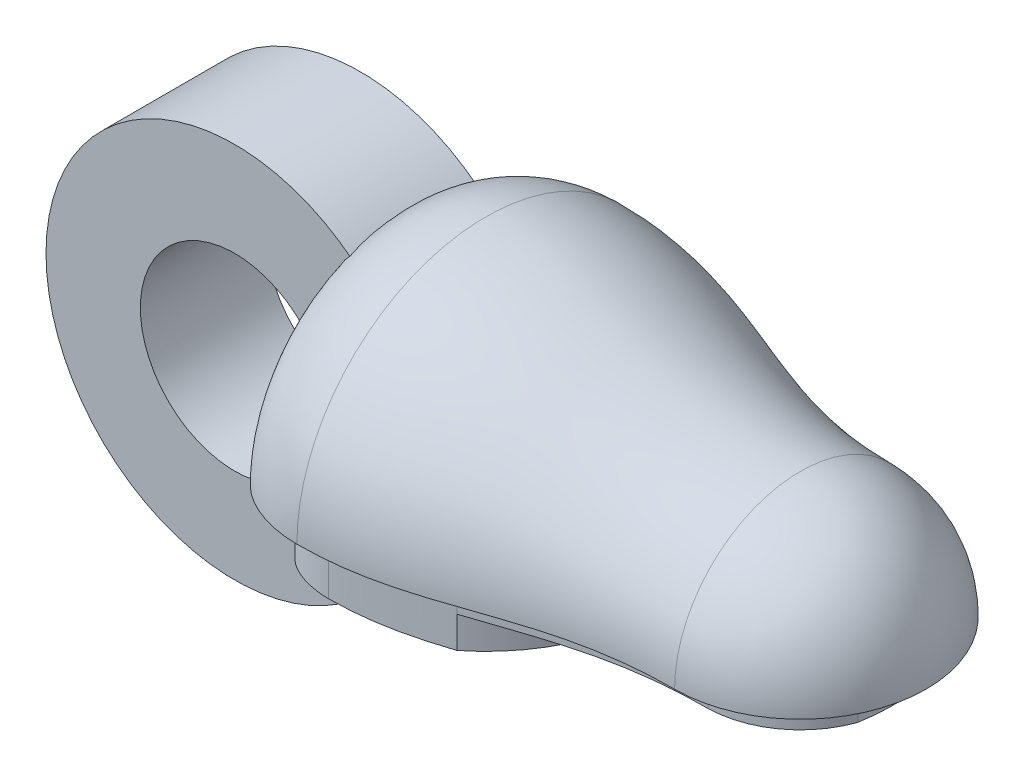
SolidWorks part; units mm, degrees
ref_plane "Front Plane" through (0, 0, 0) normal (0, 0, 1) x (1, 0, 0)
ref_plane "Top Plane" through (0, 0, 0) normal (0, 1, 0) x (1, 0, 0)
ref_plane "Right Plane" through (0, 0, 0) normal (1, 0, 0) x (0, 0, -1)
sketch "Sketch1" plane through (0, 0, 0) normal (0, 1, 0) x (1, 0, 0)
  line L0 (2.6547, 3.7704) -> (-14.3453, 3.7704) construction
  line L1 (-6.9059, 9.7814) -> (-15.9612, 9.7814) construction
  line L2 (1.6216, 7.7704) -> (-4.4887, 7.7704) construction
  line L3 (-11.3453, 5.7814) -> (-11.3453, 3.7704)
  line L4 (-11.3453, 9.7814) -> (-11.3453, 9.7704) construction
  line L5 (-11.3453, 5.7814) -> (-14.3453, 5.7814) construction
  line L6 (-14.3453, 5.7814) -> (-11.3453, 5.7814)
  line L10 (-14.3453, 7.2814) -> (-14.3453, 5.7814)
  line L11 (-10.2012, 9.7814) -> (-13.3253, 9.7814) construction
  line L12 (-14.3453, 8.6147) -> (-14.3453, 5.7234) construction
  line L13 (-11.3453, 3.7704) -> (2.6547, 3.7704)
  arc A1 (2.6547, 3.7704) -> (-1.3453, 7.7704) centre (-1.3453, 3.7704) ccw
  spline S0 degree 3 poles (-11.3453, 9.7814) (-7.4852, 9.7814) (-5.7771, 7.7704) (-1.3453, 7.7704) knots 0 0 0 0 1 1 1 1
  spline S2 degree 3 poles (-14.3453, 7.2814) (-14.3453, 9.0884) (-12.647, 9.7814) (-11.3453, 9.7814) knots 0 0 0 0 1 1 1 1
  dimension "D2" = 8
  dimension "D5" = 4
sketch "Sketch6" plane through (0, 0, 0) normal (0, 1, 0) x (1, 0, 0)
  line L0 (-11.3453, 5.7814) -> (-11.3453, 3.7704) construction
  line L2 (-11.3453, 5.7814) -> (-23.3453, 5.7814)
  line L3 (-11.3453, 5.7814) -> (-11.3453, 1.7814)
  line L4 (-11.3453, 1.7814) -> (-23.3453, 1.7814)
  line L5 (-23.3453, 5.7814) -> (-23.3453, 1.7814)
  dimension "D1" = 12
  dimension "D2" = 4
extrude "Boss-Extrude2" add sketch "Sketch6" along normal mid plane 12 contours L3 L2 L5 L4
sketch "Sketch7" plane through (0, 0, -1.7814) normal (0, 0, 1) x (1, 0, 0)
  line L0 (-11.3453, 6) -> (-23.3453, 6) construction
  line L1 (-11.3453, 6) -> (-11.3453, -6) construction
  circle A0 centre (-17.3453, 0) radius 6
  dimension "D1" = 12
extrude "Cut-Extrude-Thin2" cut sketch "Sketch7" against normal blind 12 thin contours A0 thin type one direction wall 10
sketch "Sketch8" plane through (0, 0, -1.7814) normal (0, 0, 1) x (1, 0, 0)
  line L0 (-17.3453, 0) -> (-23.3453, 0) construction
  circle A0 centre (-17.3453, 0) radius 6 construction
  circle A1 centre (-17.3453, 0) radius 3
  dimension "D1" = 6
extrude "Cut-Extrude2" cut sketch "Sketch8" against normal blind 12 contours A1
revolve "Revolve1" add sketch "Sketch1" angle 180 about L13
sketch "Sketch12" plane through (0, 0, 0) normal (0, -1, 0) x (1, 0, 0)
  line L0 (1.8139, -4.6466) -> (1.1523, -0.8942) construction
  line L1 (1.0578, -7.1825) -> (1.9084, -2.3583) construction
  line L2 (-11.3453, -1.7594) -> (-11.3453, -5.7814)
  line L3 (-13.3453, -5.7814) -> (-11.3453, -5.7814)
  line L5 (-13.3453, -7.2814) -> (-13.3453, -5.7814)
  line L6 (-11.3453, -4.7704) -> (1.4831, -4.7704)
  line L7 (-13.3453, -7.2814) -> (-13.3453, -5.7814)
  line L9 (-5.7453, -3.7704) -> (2.6547, -3.7704) construction
  line L10 (-13.3453, -0.2594) -> (-13.3453, -1.7594)
  line L11 (-13.3453, -1.7594) -> (-11.3453, -1.7594)
  line L14 (-14.3453, -7.2814) -> (-14.3453, -5.7814) construction
  arc A0 (-7.8749, -8.1654) -> (-7.8749, 0.6246) centre (-11.3453, -3.7704) ccw
  arc A2 (-1.2813, -0.7711) -> (1.4831, -2.7704) centre (-1.3453, -3.7704) cw
  arc A3 (-1.3453, -6.7704) -> (1.4831, -4.7704) centre (-1.3453, -3.7704) ccw
  arc A4 (-1.3453, -6.7704) -> (1.4831, -4.7704) centre (-1.3453, -3.7704) ccw
  spline S0 degree 3 poles (1.4831, -2.7704) (1.5752, -3.2925) (1.6249, -3.9664) (1.4831, -4.7704) knots 0 0 0 0 1 1 1 1
  spline S1 degree 3 poles (-7.8749, 0.6246) (-8.2409, 0.7438) (-8.6033, 0.8525) (-9.697, 1.1224) (-10.4513, 1.2384) (-11.3453, 1.2406) knots 0.622123 0.622123 0.622123 0.622123 0.75 0.75 1 1 1 1
  spline S2 degree 3 poles (-7.8749, -8.1654) (-8.2551, -8.2892) (-8.6307, -8.4019) (-9.7259, -8.6693) (-10.4671, -8.7814) (-11.3453, -8.7814) knots 0.615022 0.615022 0.615022 0.615022 0.75 0.75 1 1 1 1
  spline S5 degree 3 poles (-1.2813, -0.7711) (-2.4649, -0.7744) (-3.4839, -0.6413) (-5.2955, -0.2419) (-6.0864, 0.022) (-7.1837, 0.3955) (-7.5309, 0.5147) (-7.8749, 0.6246) knots 0 0 0 0 0.25 0.25 0.5 0.5 0.622123 0.622123 0.622123 0.622123
  spline S6 degree 3 poles (-11.3453, 1.2406) (-11.582, 1.2406) (-11.8493, 1.2076) (-12.3517, 1.0708) (-12.5858, 0.9673) (-12.8642, 0.7781) (-12.9452, 0.7097) (-13.0834, 0.5642) (-13.1407, 0.4874) (-13.2355, 0.3189) (-13.2734, 0.2271) (-13.3283, 0.0119) (-13.3453, -0.1119) (-13.3453, -0.2594) knots 0 0 0 0 0.25 0.25 0.5 0.5 0.625 0.625 0.75 0.75 0.875 0.875 1 1 1 1
  spline S7 degree 3 poles (3214.922, -3831.8447) (219.1857, -83.5764) (29.1768, 0.4063) (-5.358, -7.311) (-6.1481, -7.5771) (-7.6211, -8.0831) (-8.3035, -8.3221) (-33.3738, -14.4428) (-92.9111, 51.858) (-4487.7798, 2217.9717) knots -9.03718 -9.03718 -9.03718 -9.03718 0.25 0.25 0.5 0.5 0.75 0.75 9.312706 9.312706 9.312706 9.312706 only from (-1.3453, -6.7704) to (-11.3453, -8.7814)
  spline S8 degree 3 poles (-3010.8591, -5.2178) (34.6999, 43.988) (-1.9174, -11.4529) (-12.3517, -8.6116) (-12.5858, -8.5081) (-12.8642, -8.3189) (-12.9452, -8.2505) (-13.0834, -8.105) (-13.1407, -8.0282) (-13.2355, -7.8597) (-13.2734, -7.7679) (-15.0855, -0.6685) (27.3554, 74.7723) (1904.2115, 2299.524) knots -9.884767 -9.884767 -9.884767 -9.884767 0.25 0.25 0.5 0.5 0.625 0.625 0.75 0.75 0.875 0.875 8.999323 8.999323 8.999323 8.999323 only from (-11.3453, -8.7814) to (-13.3453, -7.2814)
  spline S9 degree 3 poles (-1.3453, -6.7704) (-2.5289, -6.7704) (-3.5475, -6.9064) (-5.358, -7.311) (-6.1481, -7.5771) (-7.2234, -7.9465) (-7.5508, -8.06) (-7.8749, -8.1654) knots 0 0 0 0 0.25 0.25 0.5 0.5 0.615022 0.615022 0.615022 0.615022
  spline S10 degree 3 poles (-11.3453, -8.7814) (-11.582, -8.7814) (-11.8493, -8.7484) (-12.3517, -8.6116) (-12.5858, -8.5081) (-12.8642, -8.3189) (-12.9452, -8.2505) (-13.0834, -8.105) (-13.1407, -8.0282) (-13.2355, -7.8597) (-13.2734, -7.7679) (-13.3283, -7.5527) (-13.3453, -7.4289) (-13.3453, -7.2814) knots 0 0 0 0 0.25 0.25 0.5 0.5 0.625 0.625 0.75 0.75 0.875 0.875 1 1 1 1
  line M8 (-11.3453, -1.7594) -> (-11.3453, -5.7814)
  line M9 (-11.3453, -5.7814) -> (-14.3453, -5.7814)
  line M17 (-14.3453, -1.7594) -> (-11.3453, -1.7594)
  dimension "D2" = 11.2
  dimension "D3" = 100
  dimension "D4" = 100
  dimension "D1" = 1
sketch "Sketch16" plane through (0, 0, 0) normal (0, 1, 0) x (1, 0, 0)
  arc A0 (1.4831, 4.7704) -> (-1.3453, 6.7704) centre (-1.3453, 3.7704) ccw construction
  arc A1 (-1.2813, 0.7711) -> (1.4831, 2.7704) centre (-1.3453, 3.7704) ccw construction
  arc A2 (1.4831, 4.7704) -> (-1.3453, 6.7704) centre (-1.3453, 3.7704) ccw
  arc A3 (-1.2813, 0.7711) -> (1.4831, 2.7704) centre (-1.3453, 3.7704) ccw
  arc A5 (-7.8749, -0.6246) -> (-7.8749, 8.1654) centre (-11.3453, 3.7704) ccw
  spline S0 degree 3 poles (1960.8503, 2273.914) (161.3304, 58.6008) (23.6883, 0.8202) (-5.358, 7.311) (-6.1481, 7.5771) (-30.1509, 15.8225) (0.4969, 9.7763) (-2523.9743, -1625.424) knots -7.521471 -7.521471 -7.521471 -7.521471 0.25 0.25 0.5 0.5 8.397723 8.397723 8.397723 8.397723 only from (-1.3453, 6.7704) to (-7.8749, 8.1654) construction
  spline S1 degree 3 poles (2909.8456, 733.3764) (-2947.265, -552.5826) (2979.4573, 330.4036) (-2994.9079, -46.4731) knots -27.227837 -27.227837 -27.227837 -27.227837 26.927862 26.927862 26.927862 26.927862 only from (1.4831, 2.7704) to (1.4831, 4.7704) construction
  spline S2 degree 3 poles (1954.4659, -2271.9615) (161.2468, -51.5224) (23.7692, 6.65) (-5.2955, 0.2419) (-6.0864, -0.022) (-30.1126, -8.1991) (0.5523, -2.2401) (-2519.2589, 1640.1401) knots -7.521487 -7.521487 -7.521487 -7.521487 0.25 0.25 0.5 0.5 8.397727 8.397727 8.397727 8.397727 only from (-1.2813, 0.7711) to (-7.8749, -0.6246) construction
  spline S3 degree 3 poles (-1.3453, 6.7704) (-2.5289, 6.7704) (-3.5475, 6.9064) (-5.358, 7.311) (-6.1481, 7.5771) (-7.2234, 7.9465) (-7.5508, 8.06) (-7.8749, 8.1654) knots 0 0 0 0 0.25 0.25 0.5 0.5 0.615022 0.615022 0.615022 0.615022
  spline S4 degree 3 poles (1.4831, 2.7704) (1.5752, 3.2925) (1.6249, 3.9664) (1.4831, 4.7704) knots 0 0 0 0 1 1 1 1
  spline S5 degree 3 poles (-1.2813, 0.7711) (-2.4649, 0.7744) (-3.4839, 0.6413) (-5.2955, 0.2419) (-6.0864, -0.022) (-7.1837, -0.3955) (-7.5309, -0.5147) (-7.8749, -0.6246) knots 0 0 0 0 0.25 0.25 0.5 0.5 0.622123 0.622123 0.622123 0.622123
  point P10 (0, 0)
  point P12 (0, 0)
  point P13 (0, 0)
  point P17 (0, 0)
extrude "Boss-Extrude11" add sketch "Sketch12" along normal blind 2 separate body contours S10 S2 A0 S1 S6 L10 L7 M17 M8 M9 region at (-9.753, 0, -6.6703) region at (-8.5476, 0, -2.4196) region at (-11.5803, 0, -0.2424) region at (-13.2354, 0, -6.1831)
extrude "Boss-Extrude13" add sketch "Sketch16" against normal blind 1 contours A5 S3 A2 S4 A3 S5
